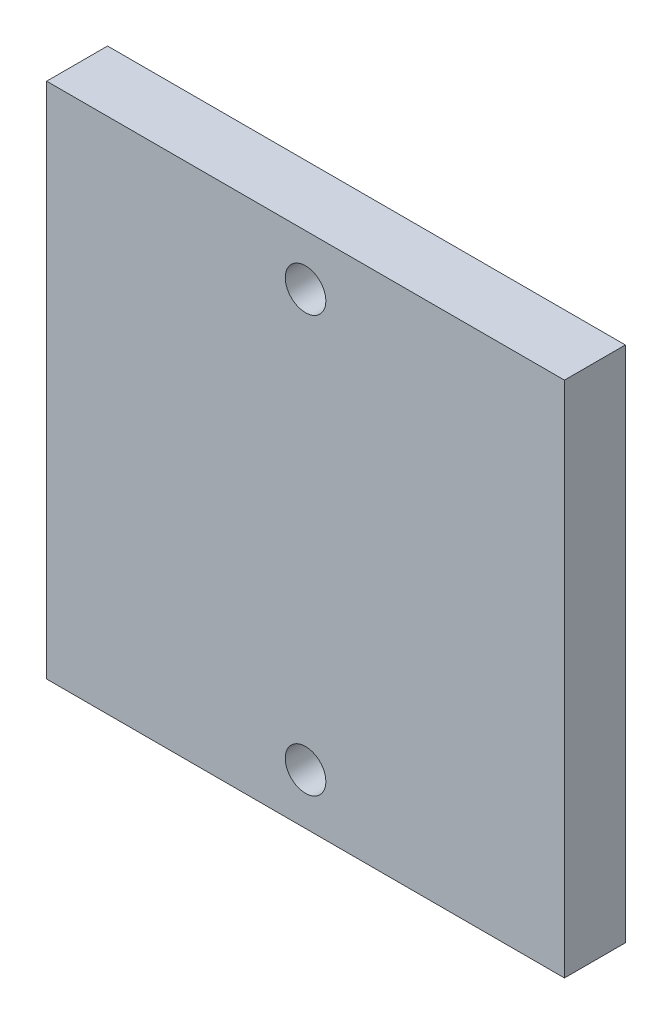
SolidWorks part; units mm, degrees
material "ABS"
ref_plane "Plano frontal" through (0, 0, 0) normal (0, 0, 1) x (1, 0, 0)
ref_plane "Plano superior" through (0, 0, 0) normal (0, 1, 0) x (1, 0, 0)
ref_plane "Plano direito" through (0, 0, 0) normal (1, 0, 0) x (0, 0, -1)
sketch "Esboço1" plane through (0, 0, 0) normal (0, 0, 1) x (1, 0, 0)
  line L1 (25.5, 25.5) -> (-25.5, 25.5)
  line L2 (25.5, 25.5) -> (25.5, -25.5)
  line L3 (25.5, -25.5) -> (-25.5, -25.5)
  line L4 (-25.5, 25.5) -> (-25.5, -25.5)
  line L5 (25.5, 25.5) -> (-25.5, -25.5) construction
  line L6 (25.5, -25.5) -> (-25.5, 25.5) construction
  point P0 (0, 0)
  dimension "D1" = 51
  dimension "D2" = 51
extrude "Ressalto-extrusão1" add sketch "Esboço1" along normal blind 6
sketch "Esboço2" plane through (0, 0, 0) normal (0, 0, -1) x (-1, 0, 0)
  line L0 (25.5, -25.5) -> (-25.5, -25.5) construction
  line L1 (-24.1, 12.4) -> (-17.6, 12.4)
  line L2 (-24.1, 12.4) -> (-24.1, -24.1)
  line L3 (-24.1, -24.1) -> (-17.6, -24.1)
  line L4 (-17.6, 12.4) -> (-17.6, -24.1)
  line L5 (-25.5, -25.5) -> (-25.5, 25.5) construction
  dimension "D1" = 6.5
  dimension "D2" = 36.5
  dimension "D3" = 1.4
  dimension "D4" = 1.4
extrude "Corte-extrusão1" cut sketch "Esboço2" against normal blind 4.5
sketch "Esboço3" plane through (0, 0, 6) normal (0, 0, 1) x (1, 0, 0)
  line L0 (25.5, 25.5) -> (-25.5, 25.5) construction
  line L1 (-25.5, -25.5) -> (25.5, -25.5) construction
  circle A0 centre (0, -20.5) radius 2
  circle A1 centre (0, 20.5) radius 2
  dimension "D1" = 4
  dimension "D2" = 5
  dimension "D3" = 5
extrude "Corte-extrusão2" cut sketch "Esboço3" against normal through all
